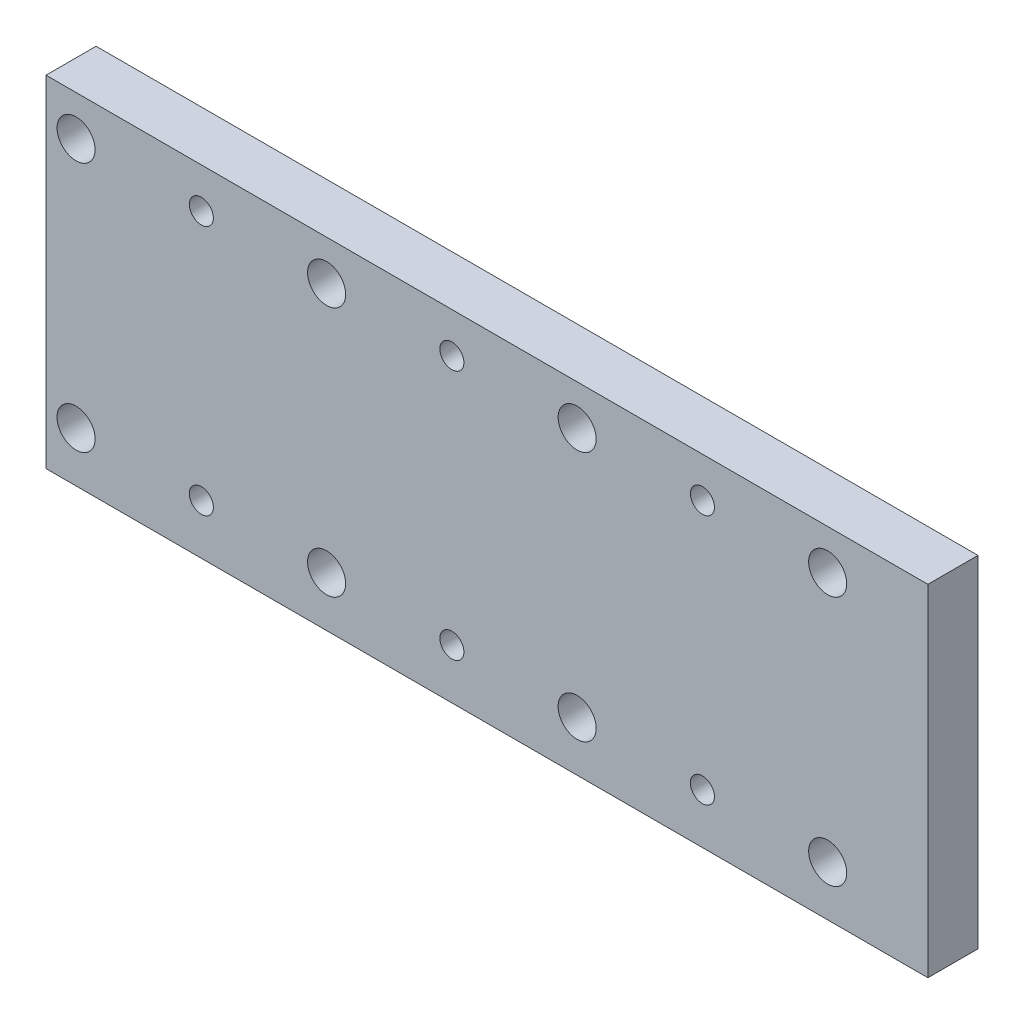
SolidWorks part; units mm, degrees
material "POM Acetal Copolymer"
ref_plane "Front Plane" through (0, 0, 0) normal (0, 0, 1) x (1, 0, 0)
ref_plane "Top Plane" through (0, 0, 0) normal (0, 1, 0) x (1, 0, 0)
ref_plane "Right Plane" through (0, 0, 0) normal (1, 0, 0) x (0, 0, -1)
sketch "Sketch1" plane through (0, 0, 0) normal (0, 0, 1) x (1, 0, 0)
  line L1 (-220, 85) -> (220, 85)
  line L2 (-220, 85) -> (-220, -85)
  line L3 (-220, -85) -> (220, -85)
  line L4 (220, 85) -> (220, -85)
  line L5 (-220, 85) -> (220, -85) construction
  line L6 (-220, -85) -> (220, 85) construction
  point P0 (0, 0)
  dimension "D1" = 440
  dimension "D2" = 170
extrude "Boss-Extrude1" add sketch "Sketch1" along normal blind 25
sketch "Sketch2" plane through (0, 0, 25) normal (0, 0, 1) x (1, 0, 0)
  line L0 (-220, -85) -> (220, -85) construction
  line L5 (-220, 85) -> (-220, -85) construction
  line L6 (-220, 0) -> (220, 0) construction
  line L7 (220, -85) -> (220, 85) construction
  line L37 (0, -85) -> (0, 85) construction
  line L42 (220, 85) -> (-220, 85) construction
  circle A20 centre (170, 65) radius 9.5
  circle A21 centre (45, 65) radius 9.5
  circle A22 centre (-80, 65) radius 9.5
  circle A23 centre (-205, 65) radius 9.5
  circle A24 centre (45, -60) radius 9.5
  circle A25 centre (-80, -60) radius 9.5
  circle A26 centre (-205, -60) radius 9.5
  circle A27 centre (170, -60) radius 9.5
  dimension "D10" = 19
  dimension "D2" = 4
  dimension "D3" = 2
  dimension "D4" = 125
  dimension "D6" = 50
  dimension "D11" = 20
  dimension "D12" = 50
  dimension "D5" = 125
extrude "Cut-Extrude1" cut sketch "Sketch2" against normal blind 15
sketch "Sketch4" plane through (0, 0, 10) normal (0, 0, 1) x (1, 0, 0)
  line L1 (170, -60) -> (170, 65) construction
  circle A0 centre (170, 65) radius 6
  circle A1 centre (45, 65) radius 6
  circle A2 centre (-80, 65) radius 6
  circle A3 centre (-205, 65) radius 6
  circle A4 centre (45, -60) radius 6
  circle A5 centre (-80, -60) radius 6
  circle A6 centre (-205, -60) radius 6
  circle A7 centre (170, -60) radius 6
  dimension "D1" = 12
  dimension "D4" = 125
  dimension "D5" = 125
  dimension "D2" = 4
  dimension "D3" = 2
extrude "Cut-Extrude3" cut sketch "Sketch4" against normal through all
sketch "Sketch3" plane through (0, 0, 0) normal (0, 0, -1) x (-1, 0, 0)
  line L5 (-170, -60) -> (-45, -60) construction
  circle A16 centre (-107.5, -60) radius 9.5
  circle A17 centre (17.5, -60) radius 9.5
  circle A18 centre (142.5, -60) radius 9.5
  circle A19 centre (17.5, 65) radius 9.5
  circle A20 centre (142.5, 65) radius 9.5
  circle A21 centre (-107.5, 65) radius 9.5
  dimension "D1" = 19
  dimension "D2" = 2
extrude "Cut-Extrude2" cut sketch "Sketch3" against normal blind 15
sketch "Sketch5" plane through (0, 0, 15) normal (0, 0, -1) x (-1, 0, 0)
  line L0 (-170, 65) -> (-45, 65) construction
  circle A0 centre (-107.5, -60) radius 6
  circle A1 centre (17.5, -60) radius 6
  circle A2 centre (142.5, -60) radius 6
  circle A3 centre (17.5, 65) radius 6
  circle A4 centre (142.5, 65) radius 6
  circle A5 centre (-107.5, 65) radius 6
  dimension "D1" = 12
  dimension "D3" = 125
  dimension "D2" = 2
extrude "Cut-Extrude4" cut sketch "Sketch5" against normal through all
sketch3d "3DSketch1"
  point P0 (-220, 85, -2.5)
